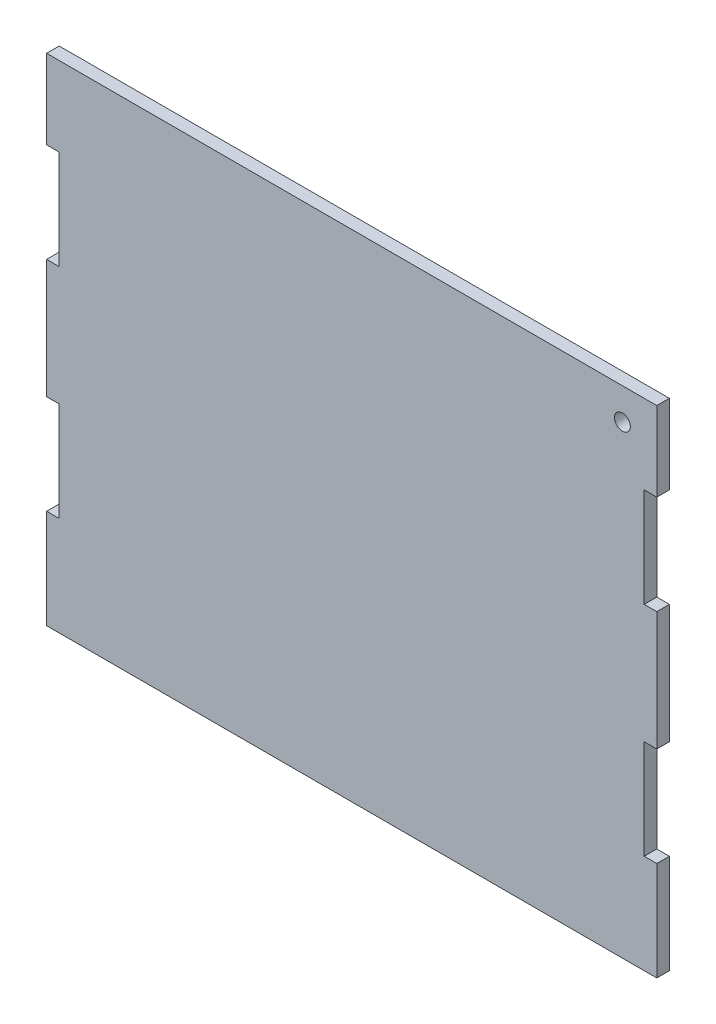
SolidWorks part; units mm, degrees
material "Beech"
ref_plane "Front Plane" through (0, 0, 0) normal (0, 0, 1) x (1, 0, 0)
ref_plane "Top Plane" through (0, 0, 0) normal (0, 1, 0) x (1, 0, 0)
ref_plane "Right Plane" through (0, 0, 0) normal (1, 0, 0) x (0, 0, -1)
sketch "Sketch1" plane through (0, 0, 0) normal (0, 0, 1) x (1, 0, 0)
  line L1 (0, 0) -> (307.7, 0)
  line L2 (0, 0) -> (0, 250)
  line L3 (0, 250) -> (307.7, 250)
  line L4 (307.7, 0) -> (307.7, 250)
  dimension "D1" = 250
  dimension "D2" = 307.7
extrude "Boss-Extrude1" add sketch "Sketch1" along normal blind 6.35
sketch "Sketch2" plane through (0, 0, 6.35) normal (0, 0, 1) x (1, 0, 0)
  line L0 (307.7, 0) -> (307.7, 250) construction
  line L1 (307.7, 50) -> (301.35, 50)
  line L2 (307.7, 50) -> (307.7, 100)
  line L3 (307.7, 100) -> (301.35, 100)
  line L4 (301.35, 50) -> (301.35, 100)
  line L5 (0, 0) -> (307.7, 0) construction
  line L6 (307.7, 160) -> (307.7, 210)
  line L7 (307.7, 160) -> (301.35, 160)
  line L8 (301.35, 160) -> (301.35, 210)
  line L9 (307.7, 210) -> (301.35, 210)
  line L10 (307.7, 250) -> (0, 250) construction
  line L11 (0, 250) -> (0, 0) construction
  line L12 (0, 50) -> (6.35, 50)
  line L13 (0, 50) -> (0, 100)
  line L14 (0, 100) -> (6.35, 100)
  line L15 (6.35, 50) -> (6.35, 100)
  line L16 (0, 160) -> (0, 210)
  line L17 (0, 160) -> (6.35, 160)
  line L18 (6.35, 160) -> (6.35, 210)
  line L19 (0, 210) -> (6.35, 210)
  line L20 (301.35, 250) -> (301.35, 0) construction
  circle A0 centre (290.35, 234.125) radius 4
  dimension "D11" = 8
  dimension "D1" = 6.35
  dimension "D2" = 50
  dimension "D3" = 50
  dimension "D5" = 40
  dimension "D6" = 6.35
  dimension "D7" = 50
  dimension "D8" = 50
  dimension "D10" = 40
  dimension "D12" = 11
  dimension "D13" = 15.875
  dimension "D4" = 2
  dimension "D9" = 2
extrude "Cut-Extrude1" cut sketch "Sketch2" against normal through all
